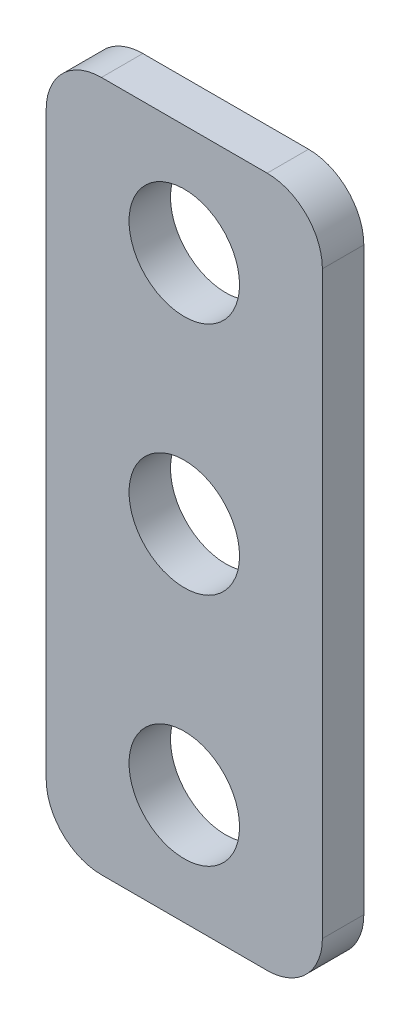
SolidWorks part; units mm, degrees
note: The reader was unsure of these and kept them because the rebuilt part matched: thickness of "基体-法兰1", "钣金1", "钣金2".
ref_plane "前视基准面" through (0, 0, 0) normal (0, 0, 1) x (1, 0, 0)
ref_plane "上视基准面" through (0, 0, 0) normal (0, 1, 0) x (1, 0, 0)
ref_plane "右视基准面" through (0, 0, 0) normal (1, 0, 0) x (0, 0, -1)
sketch "草图1" plane through (0, 0, 0) normal (0, 0, 1) x (1, 0, 0)
  line L1 (-10, -25) -> (10, -25)
  line L2 (-10, -25) -> (-10, 25)
  line L3 (-10, 25) -> (10, 25)
  line L4 (10, -25) -> (10, 25)
  line L5 (-10, -25) -> (10, 25) construction
  line L6 (-10, 25) -> (10, -25) construction
  point P0 (0, 0)
  dimension "D1" = 50
  dimension "D2" = 20
base flange "基体-法兰1" sketch "草图1" thickness 3 reverse thickness direction no parameters "D1"=10
sketch "草图6" plane through (0, 0, 0) normal (0, 0, 1) x (1, 0, 0)
  line L0 (10, 25) -> (-10, 25) construction
  line L1 (-10, -25) -> (10, -25) construction
  circle A0 centre (0, 17) radius 4
  circle A2 centre (0, -17) radius 4
  circle A3 centre (0, 0) radius 4
  point P11 (0, -17.9106)
  dimension "D1" = 8
  dimension "D2" = 8
  dimension "D3" = 8
  dimension "D4" = 8
  dimension "D5" = 8
  dimension "D6" = 0
extrude "切除-拉伸1" cut sketch "草图6" against normal blind 10 normal cut yes
fillet "圆角1" radius 4 4 edges at (10, -25, -1.5) (-10, -25, -1.5) (-10, 25, -1.5) (10, 25, -1.5)
sketch "折弯-线1" [suppressed] plane through (0, 0, 0) normal (0, 1, 0) x (1, 0, 0)
sketch "边界框1" [suppressed] plane through (0, 0, 0) normal (0, 1, 0) x (1, 0, 0)
sheet metal parameters "钣金1" thickness 3 parameters "D1"=10
flat pattern "平板型式1" [suppressed]
sketch "折弯-线2" plane through (0, 0, 0) normal (0, 1, 0) x (1, 0, 0)
sketch3d "边界框2" [suppressed]
  line L0 (10, -35, 0) -> (10, 35, 0) construction
  line L1 (-10, -35, 0) -> (-10, 35, 0) construction
  line L2 (10, -35, 0) -> (-10, -35, 0) construction
  line L3 (10, 35, 0) -> (-10, 35, 0) construction
sheet metal parameters "钣金2" thickness 3 parameters "D1"=10
flat pattern "平板型式1"
sketch "折弯-线2" plane through (0, 0, 0) normal (0, 1, 0) x (1, 0, 0)
sketch3d "边界框2" [suppressed]
  line L0 (10, -25, 0) -> (10, 25, 0) construction
  line L1 (-10, -25, 0) -> (-10, 25, 0) construction
  line L2 (10, -25, 0) -> (-10, -25, 0) construction
  line L3 (10, 25, 0) -> (-10, 25, 0) construction
